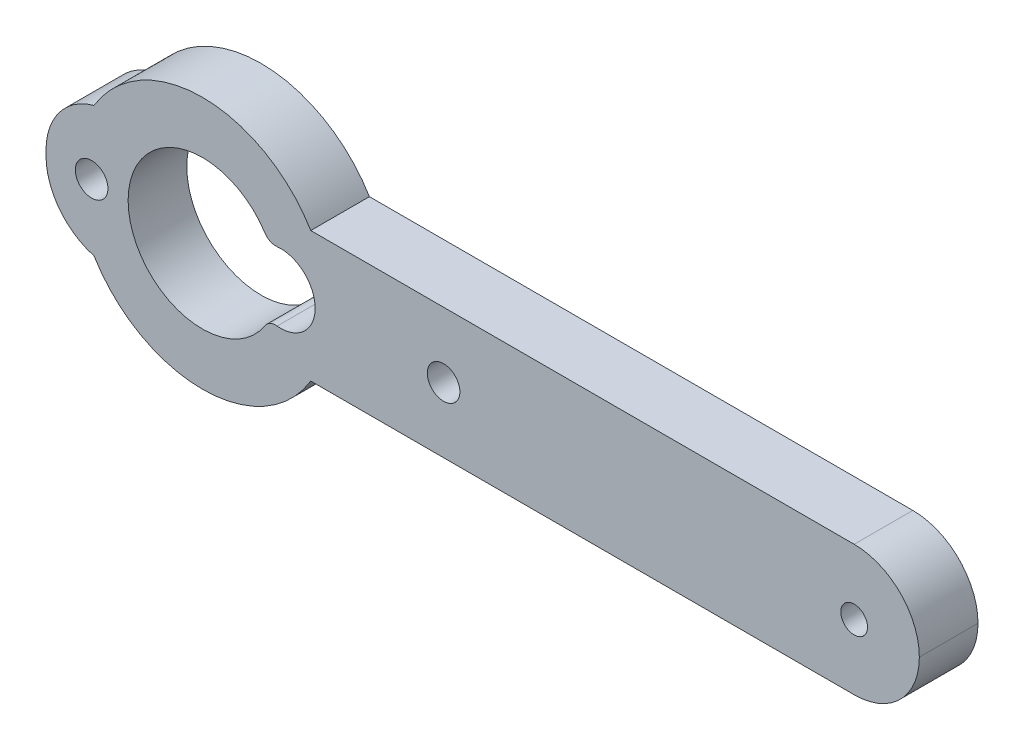
SolidWorks part; units mm, degrees
ref_plane "前视基准面" through (0, 0, 0) normal (0, 0, 1) x (1, 0, 0)
ref_plane "上视基准面" through (0, 0, 0) normal (0, 1, 0) x (1, 0, 0)
ref_plane "右视基准面" through (0, 0, 0) normal (1, 0, 0) x (0, 0, -1)
sketch "草图1" plane through (0, 0, 0) normal (0, 0, 1) x (1, 0, 0)
  line L0 (-63.312, 0) -> (-67, 0)
  line L1 (0, 0) -> (-46.688, 0)
  line L2 (0, 0) -> (0, -10)
  line L3 (0, -10) -> (-46.688, -10)
  line L4 (-67, 0) -> (-67, -10)
  line L5 (-63.312, -10) -> (-67, -10)
  arc A0 (-49.8777, -2.4996) -> (-49.8777, -7.5004) centre (-55, -5) ccw
  circle A1 centre (-5, -5) radius 1.025
  arc A2 (-46.688, 0) -> (-63.312, 0) centre (-55, -5) ccw
  circle A3 centre (-55, -5) radius 9.7 construction
  arc A4 (-63.312, -10) -> (-46.688, -10) centre (-55, -5) ccw
  arc A5 (-49.8777, -7.5004) -> (-49.8777, -2.4996) centre (-49, -5) ccw
  circle A6 centre (-55, -5) radius 5.7 construction
  circle A7 centre (-63.5, -5) radius 1.25
  circle A8 centre (-36.5, -5) radius 1.25
  dimension "D6" = 2.05
  dimension "D8" = 11.4
  dimension "D11" = 5.3
  dimension "D13" = 2.5
  dimension "D15" = 2.5
  dimension "D1" = 12
  dimension "D2" = 10
  dimension "D3" = 5
  dimension "D4" = 5
  dimension "D5" = 5
  dimension "D7" = 50
  dimension "D10" = 6
  dimension "D12" = 8.5
  dimension "D14" = 27
  dimension "D9" = 4
extrude "凸台-拉伸1" add sketch "草图1" along normal blind 4.5
fillet "圆角1" radius 1 2 edges at (-49.8777, -7.5004, 2.25) (-49.8777, -2.4996, 2.25)
fillet "圆角2" radius 5 2 edges at (0, -10, 2.25) (0, 0, 2.25)
fillet "圆角3" radius 5 2 edges at (-67, 0, 2.25) (-67, -10, 2.25)
